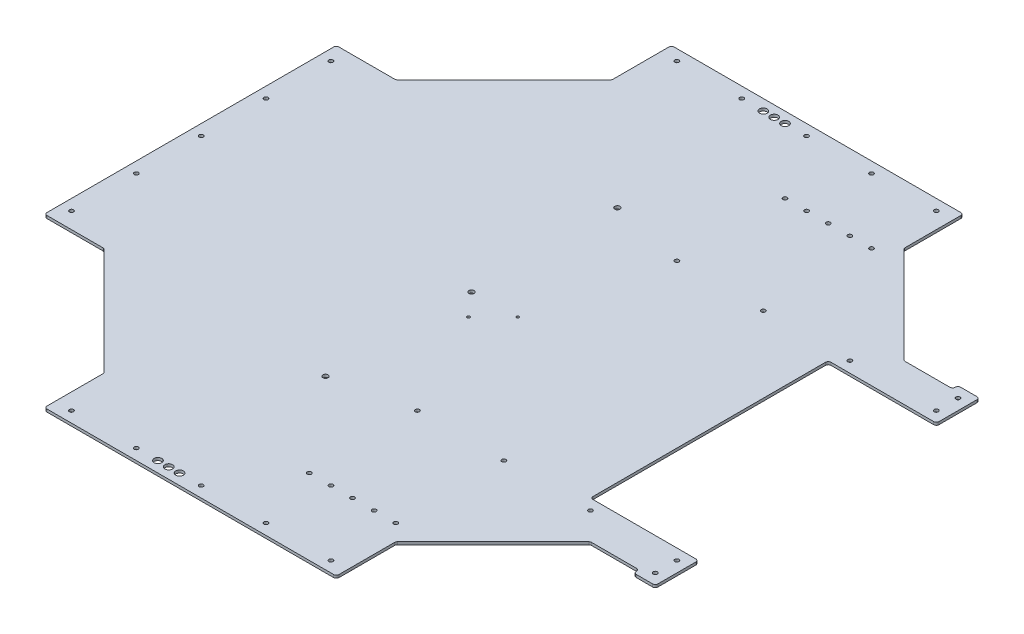
SolidWorks part; units mm, degrees
material "6061-T6 (SS)"
ref_plane "Front Plane" through (0, 0, 0) normal (0, 0, 1) x (1, 0, 0)
ref_plane "Top Plane" through (0, 0, 0) normal (0, 1, 0) x (1, 0, 0)
ref_plane "Right Plane" through (0, 0, 0) normal (1, 0, 0) x (0, 0, -1)
sketch "Sketch1" plane through (0, 0, 0) normal (0, 1, 0) x (1, 0, 0)
  line L0 (368.3, 171.45) -> (368.3, -171.45)
  line L1 (-368.3, 368.3) -> (368.3, 368.3) construction
  line L2 (-368.3, 368.3) -> (-368.3, -368.3) construction
  line L3 (-368.3, -368.3) -> (368.3, -368.3) construction
  line L4 (368.3, 368.3) -> (368.3, -368.3) construction
  line L5 (-368.3, 368.3) -> (368.3, -368.3) construction
  line L6 (-368.3, -368.3) -> (368.3, 368.3) construction
  line L7 (-171.45, 368.3) -> (171.45, 368.3)
  line L8 (-368.3, 171.45) -> (-368.3, -171.45)
  line L9 (-171.45, -368.3) -> (171.45, -368.3)
  line L10 (368.3, 171.45) -> (298.45, 171.45)
  line L11 (298.45, 171.45) -> (171.45, 298.45)
  line L12 (171.45, 298.45) -> (171.45, 368.3)
  line L13 (-171.45, 368.3) -> (-171.45, 298.45)
  line L14 (-171.45, 298.45) -> (-298.45, 171.45)
  line L15 (-298.45, 171.45) -> (-368.3, 171.45)
  line L16 (-368.3, -171.45) -> (-298.45, -171.45)
  line L17 (-298.45, -171.45) -> (-171.45, -298.45)
  line L18 (-171.45, -298.45) -> (-171.45, -368.3)
  line L19 (171.45, -368.3) -> (171.45, -298.45)
  line L20 (171.45, -298.45) -> (298.45, -171.45)
  line L21 (298.45, -171.45) -> (368.3, -171.45)
  line L22 (-355.6, 171.45) -> (-355.6, -171.45) construction
  line L23 (-355.6, -152.4) -> (-355.6, -76.2) construction
  line L24 (368.3, -139.7) -> (241.3, -139.7)
  line L25 (241.3, -139.7) -> (241.3, 139.7)
  line L26 (241.3, 139.7) -> (368.3, 139.7)
  line L27 (298.45, -171.45) -> (298.45, -139.7) construction
  line L28 (298.45, 171.45) -> (298.45, 139.7) construction
  line L29 (368.3, 171.45) -> (368.3, 184.15)
  line L30 (368.3, 184.15) -> (285.75, 184.15)
  line L31 (368.3, -171.45) -> (368.3, -184.15)
  line L32 (368.3, -184.15) -> (285.75, -184.15)
  line L33 (368.3, 184.15) -> (368.3, 190.5)
  line L34 (368.3, 190.5) -> (342.9, 190.5)
  line L35 (342.9, 190.5) -> (342.9, 184.15)
  line L36 (368.3, -184.15) -> (368.3, -190.5)
  line L37 (368.3, -190.5) -> (342.9, -190.5)
  line L38 (342.9, -190.5) -> (342.9, -184.15)
  line L39 (152.4, 279.4) -> (127, 279.4) construction
  circle A0 centre (-355.6, -152.4) radius 2.413
  circle A1 centre (-355.6, -76.2) radius 2.413
  circle A2 centre (-355.6, 0) radius 2.413
  circle A3 centre (-355.6, 76.2) radius 2.413
  circle A4 centre (-355.6, 152.4) radius 2.413
  circle A27 centre (-76.2, -355.6) radius 2.413
  circle A28 centre (0, -355.6) radius 2.413
  circle A103 centre (-152.4, -355.6) radius 2.413
  circle A104 centre (76.2, -355.6) radius 2.413
  circle A105 centre (152.4, -355.6) radius 2.413
  circle A106 centre (-152.4, 355.6) radius 2.413
  circle A107 centre (-76.2, 355.6) radius 2.413
  circle A108 centre (0, 355.6) radius 2.413
  circle A109 centre (76.2, 355.6) radius 2.413
  circle A110 centre (152.4, 355.6) radius 2.413
  circle A111 centre (355.6, 152.4) radius 2.413
  circle A112 centre (355.6, 76.2) radius 2.413
  circle A113 centre (355.6, 0) radius 2.413
  circle A114 centre (355.6, -76.2) radius 2.413
  circle A115 centre (355.6, -152.4) radius 2.413
  circle A116 centre (355.6, -177.8) radius 2.413
  circle A117 centre (355.6, 177.8) radius 2.413
  circle A118 centre (254, -152.4) radius 2.413
  circle A119 centre (254, 152.4) radius 2.413
  circle A120 centre (152.4, -152.4) radius 2.413
  circle A121 centre (152.4, 152.4) radius 2.413
  circle A122 centre (50.8, -152.4) radius 2.413
  circle A123 centre (50.8, 152.4) radius 2.413
  circle A124 centre (152.4, 279.4) radius 2.413
  circle A125 centre (152.4, -279.4) radius 2.413
  circle A126 centre (127, 279.4) radius 2.413
  circle A127 centre (127, -279.4) radius 2.413
  circle A128 centre (101.6, 279.4) radius 2.413
  circle A129 centre (101.6, -279.4) radius 2.413
  circle A130 centre (76.2, 279.4) radius 2.413
  circle A131 centre (76.2, -279.4) radius 2.413
  circle A132 centre (50.8, 279.4) radius 2.413
  circle A133 centre (50.8, -279.4) radius 2.413
  point P0 (0, 0)
  point P15 (-368.3, 0)
  dimension "D5" = 4.826
  dimension "D11" = 4.826
  dimension "D12" = 342.9
  dimension "D24" = 6.35
  dimension "D26" = 4.826
  dimension "D1" = 736.6
  dimension "D2" = 196.85
  dimension "D3" = 69.85
  dimension "D4" = 12.7
  dimension "D6" = 19.05
  dimension "D8" = 76.2
  dimension "D10" = 19.05
  dimension "D9" = 12.7
  dimension "D13" = 5
  dimension "D14" = 76.2
  dimension "D15" = 279.4
  dimension "D16" = 25.4
  dimension "D17" = 127
  dimension "D18" = 6.35
  dimension "D19" = 25.4
  dimension "D20" = 6.35
  dimension "D21" = 6.35
  dimension "D22" = 25.4
  dimension "D23" = 25.4
  dimension "D27" = 5
  dimension "D28" = 127
  dimension "D29" = 127
  dimension "D30" = 101.6
  dimension "D31" = 25.4
  dimension "D7" = 5
  dimension "D25" = 4
extrude "Boss-Extrude2" add sketch "Sketch1" along normal blind 3.175 contours L25 L26 L0 L10 L11 L12 L7 L13 L14 L15 L8 L16 L17 L18 L9 L19 L20 L21 L24 A111 A109 A107 A0 A1 A2 A3 A4 A27 A28 A103 A104 A105 A106 A108 | L29 L30 L11 L10 A117 | L32 L31 L21 L20 A116 | L38 L37 L36 L32 | L34 L35 L30 L33 region at (-28.2247, 0, 0) region at (329.6207, 0, -177.9798) region at (355.6, 0, -187.325) region at (329.6207, 0, 177.9798) region at (355.6, 0, 187.325)
fillet "Fillet2" radius 3.175 24 edges at (171.45, 1.5875, 298.45) (-171.45, 1.5875, 368.3) (-171.45, 1.5875, 298.45) (-298.45, 1.5875, 171.45) (-368.3, 1.5875, 171.45) (-368.3, 1.5875, -171.45) (-298.45, 1.5875, -171.45) (-171.45, 1.5875, -298.45) (-171.45, 1.5875, -368.3) (171.45, 1.5875, -368.3) (171.45, 1.5875, -298.45) (171.45, 1.5875, 368.3) (241.3, 1.5875, 139.7) (368.3, 1.5875, 139.7) (285.75, 1.5875, 184.15) (285.75, 1.5875, -184.15) (368.3, 1.5875, -139.7) (241.3, 1.5875, -139.7) (342.9, 1.5875, 190.5) (342.9, 1.5875, 184.15) (342.9, 1.5875, -184.15) (342.9, 1.5875, -190.5) (368.3, 1.5875, -190.5) (368.3, 1.5875, 190.5)
sketch "Sketch2" plane through (0, 3.175, 0) normal (0, 1, 0) x (1, 0, 0)
  circle A0 centre (14.478, 1.778) radius 1.632
  circle A1 centre (-14.478, -27.178) radius 1.632
  arc A2 (12.846, 1.778) -> (16.1099, 1.778) centre (14.478, 1.778) ccw construction
extrude "Cut-Extrude1" cut sketch "Sketch2" against normal blind 5.08
sketch "Sketch3" plane through (0, 0, 0) normal (0, -1, 0) x (1, 0, 0)
  line L0 (-168.275, -368.3) -> (168.275, -368.3) construction
  line L1 (-1000, 0) -> (49000, 0) construction
  circle A3 centre (-25.4, -355.6) radius 4.445
  circle A4 centre (-38.1, -355.6) radius 4.445
  circle A5 centre (-50.8, -355.6) radius 4.445
  circle A6 centre (0, -355.6) radius 2.413 construction
  circle A7 centre (-50.8, 355.6) radius 4.445
  circle A8 centre (-38.1, 355.6) radius 4.445
  circle A9 centre (-25.4, 355.6) radius 4.445
  dimension "D4" = 8.89
  dimension "D1" = 25.4
  dimension "D2" = 12.7
  dimension "D3" = 12.7
  dimension "D5" = 12.7
extrude "Cut-Extrude2" cut sketch "Sketch3" against normal blind 5.08
ref_plane "Plane1" through (0, 0, 0) normal (0, 0, 1) x (1, 0, 0)
sketch "Sketch8" plane through (0, 3.175, 0) normal (0, 1, 0) x (1, 0, 0)
  line L0 (-1.7463, 0) -> (1.7463, 0) construction
  circle A0 centre (-38.1, -171.45) radius 3.048
  circle A1 centre (-38.1, -355.6) radius 4.445 construction
  circle A2 centre (-38.1, 171.45) radius 3.048
  circle A3 centre (-38.1, 0) radius 3.048
  dimension "D1" = 184.15
  dimension "D2" = 6.096
  dimension "D3" = 6.096
extrude "Cut-Extrude3" cut sketch "Sketch8" against normal blind 16.256
